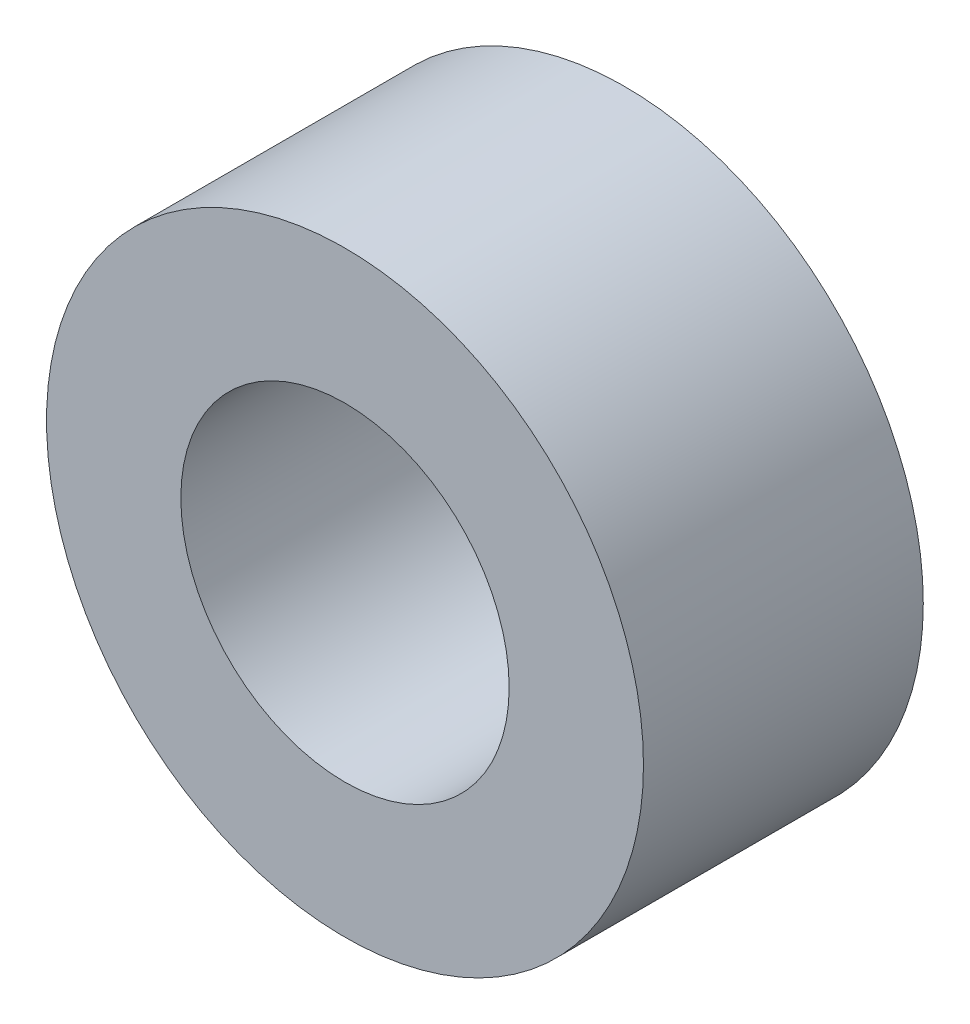
SolidWorks part; units mm, degrees
ref_plane "Front Plane" through (0, 0, 0) normal (0, 0, 1) x (1, 0, 0)
ref_plane "Top Plane" through (0, 0, 0) normal (0, 1, 0) x (1, 0, 0)
ref_plane "Right Plane" through (0, 0, 0) normal (1, 0, 0) x (0, 0, -1)
sketch "Sketch1" plane through (0, 0, 0) normal (0, 0, 1) x (1, 0, 0)
  circle A0 centre (0, 0) radius 8
  dimension "D1" = 16
extrude "Boss-Extrude2" add sketch "Sketch1" along normal blind 7.5
hole_wizard "M10x1.25 Tapped Hole1" positions "3DSketch1" profile "Sketch2" tap size "M10x1.25" standard "ISO" end condition up to next
sketch3d "3DSketch1"
  line L2 (0, 0, 7.5) -> (8, 0, 7.5) construction
  line L4 (0, 0, 7.5) -> (0, -8, 7.5) construction
  circle A0 centre (0, 0, 7.5) radius 8 construction
  point P0 (0, 0, 7.5)
  point P7 (0, 0, 15.5)
  dimension "D1" = 8
  dimension "D2" = 8
sketch "Sketch2" plane through (0, 0, 7.5) normal (1, 0, 0) x (0, -1, 0)
  line L0 (0, 0) -> (0, 7.5)
  line L1 (0, 7.5) -> (4.4, 7.5)
  line L2 (4.4, 7.5) -> (4.4, 0)
  line L5 (4.4, 0) -> (0, 0)
  line L11 (0, -6.35) -> (0, 107.95) construction
  dimension "Thru Tap Drill Dia." = 8.8
  dimension "Thru Tap Drill Depth" = 7.5
cosmetic thread "Hole Thread1"
